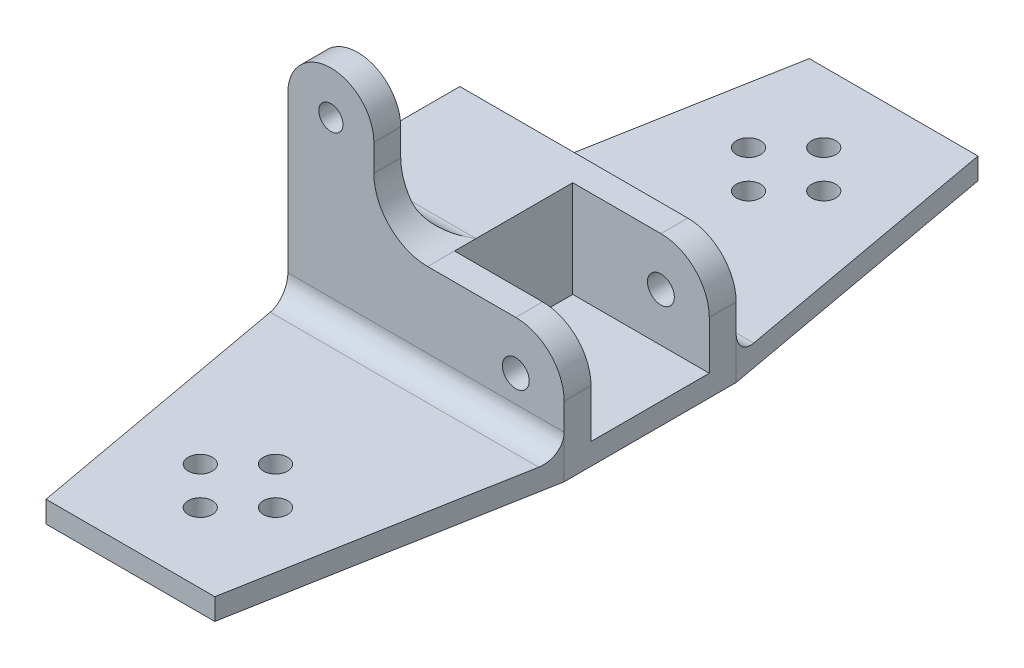
SolidWorks part; units mm, degrees
ref_plane "Ön Düzlem" through (0, 0, 0) normal (0, 0, 1) x (1, 0, 0)
ref_plane "Üst Düzlem" through (0, 0, 0) normal (0, 1, 0) x (1, 0, 0)
ref_plane "Sağ Düzlem" through (0, 0, 0) normal (1, 0, 0) x (0, 0, -1)
sketch "Sketch1" plane through (0, 0, 0) normal (0, 0, 1) x (1, 0, 0)
  line L0 (-21.2, 0) -> (21.2, 0) construction
  line L1 (-21.2, 33) -> (-21.2, 22)
  line L2 (-31.2, 12) -> (-27.5, 12) construction
  line L3 (-5.2, 33) -> (-5.2, 28)
  line L4 (4.8, 18) -> (21.2, 18)
  line L5 (-21.2, 22) -> (-21.2, 0)
  line L6 (-27.5, 0) -> (-21.2, 0) construction
  line L7 (30.2, 9) -> (30.2, -4)
  line L8 (30.2, -4) -> (-21.2, -4)
  line L9 (-21.2, -4) -> (-21.2, 0)
  arc A0 (30.2, 9) -> (21.2, 18) centre (21.2, 9) ccw
  arc A1 (-27.5, 0) -> (-27.5, 12) centre (-27.5, 6) cw construction
  circle A2 centre (21.2, 9) radius 2.5
  circle A4 centre (-13.2, 33) radius 2.25
  circle A5 centre (-13.2, 33) radius 8 construction
  arc A6 (-21.2, 33) -> (-5.2, 33) centre (-13.2, 33) cw
  arc A7 (-5.2, 28) -> (4.8, 18) centre (4.8, 28) ccw
  arc A8 (-21.2, 22) -> (-31.2, 12) centre (-31.2, 22) cw construction
  arc A9 (21.2, 0) -> (30.2, 9) centre (21.2, 9) ccw construction
  point P3 (0, 0)
  dimension "D2" = 9
  dimension "D3" = 6
  dimension "D4" = 4.5
  dimension "D5" = 5
  dimension "D6" = 33
  dimension "D8" = 16
  dimension "D9" = 10
  dimension "D1" = 42.4
  dimension "D7" = 34.4
  dimension "D10" = 4
extrude "Boss-Extrude1" add sketch "Sketch1" along normal mid plane 32
sketch "草图2" plane through (0, 0, 16) normal (0, 0, 1) x (1, 0, 0)
  line L0 (-21.2, 33) -> (-21.2, -4) construction
  line L1 (30.2, -4) -> (-21.2, -4)
  line L2 (30.2, -4) -> (30.2, 0)
  line L3 (30.2, 0) -> (-21.2, 0)
  line L4 (-21.2, -4) -> (-21.2, 0)
  dimension "D1" = 4
extrude "凸台-拉伸1" add sketch "草图2" along normal blind 55
ref_plane "基准面1" through (0, 0, 0) normal (0, 0, 1) x (1, 0, 0)
sketch "草图3" plane through (0, 0, 0) normal (0, 1, 0) x (1, 0, 0)
  line L0 (4.5, -51) -> (4.5, -71) construction
  line L1 (30.2, -71) -> (-21.2, -71) construction
  line L2 (30.2, -16) -> (20.2, -71)
  line L3 (20.2, -71) -> (30.2, -71)
  line L4 (30.2, -71) -> (30.2, -16)
  line L5 (-21.2, -16) -> (-11.2, -71)
  line L6 (-11.2, -71) -> (-21.2, -71)
  line L7 (-21.2, -71) -> (-21.2, -16)
  circle A0 centre (4.5, -51) radius 7 construction
  circle A1 centre (11.5, -51) radius 2.25
  circle A2 centre (4.5, -44) radius 2.25
  circle A3 centre (4.5, -58) radius 2.25
  circle A4 centre (-2.5, -51) radius 2.25
  dimension "D1" = 14
  dimension "D2" = 4.5
  dimension "D3" = 20
  dimension "D4" = 10
  dimension "D5" = 10
extrude "切除-拉伸2" cut sketch "草图3" against normal blind 55
mirror "镜向1" about plane through (0, 0, 0) normal (0, 0, 1) of "切除-拉伸2", "凸台-拉伸1"
sketch "草图6" plane through (0, 0, 0) normal (0, 0, 1) x (1, 0, 0)
  line L0 (4.8, 18) -> (4.8, 0)
  line L1 (20.2, 0) -> (-11.2, 0) construction
  line L2 (4.8, 0) -> (30.2, 0)
  line L3 (30.2, 0) -> (20.2, 0) construction
  line L4 (30.2, -4) -> (30.2, 0) construction
  line L5 (30.2, 0) -> (30.2, 9)
  line L6 (21.2, 18) -> (4.8, 18)
  arc A0 (30.2, 9) -> (21.2, 18) centre (21.2, 9) ccw
extrude "切除-拉伸3" cut sketch "草图6" against normal mid plane 22
sketch "草图7" plane through (0, 0, -16) normal (0, 0, -1) x (-1, 0, 0)
  line L0 (-4.8, 18) -> (21.2, 18)
  line L1 (21.2, 33) -> (21.2, 0) construction
  line L2 (21.2, 18) -> (21.2, 33)
  line L3 (5.2, 28) -> (5.2, 33) construction
  line L4 (5.2, 28) -> (5.2, 33)
  arc A0 (-4.8, 18) -> (5.2, 28) centre (-4.8, 28) ccw construction
  arc A1 (21.2, 33) -> (5.2, 33) centre (13.2, 33) ccw construction
  arc A2 (-4.8, 18) -> (5.2, 28) centre (-4.8, 28) ccw
  arc A3 (21.2, 33) -> (5.2, 33) centre (13.2, 33) ccw
extrude "切除-拉伸4" cut sketch "草图7" against normal blind 27
fillet "圆角1" radius 4 3 edges at (-8.2, 18, 11) (4.5, 0, -16) (4.5, 0, 16)
